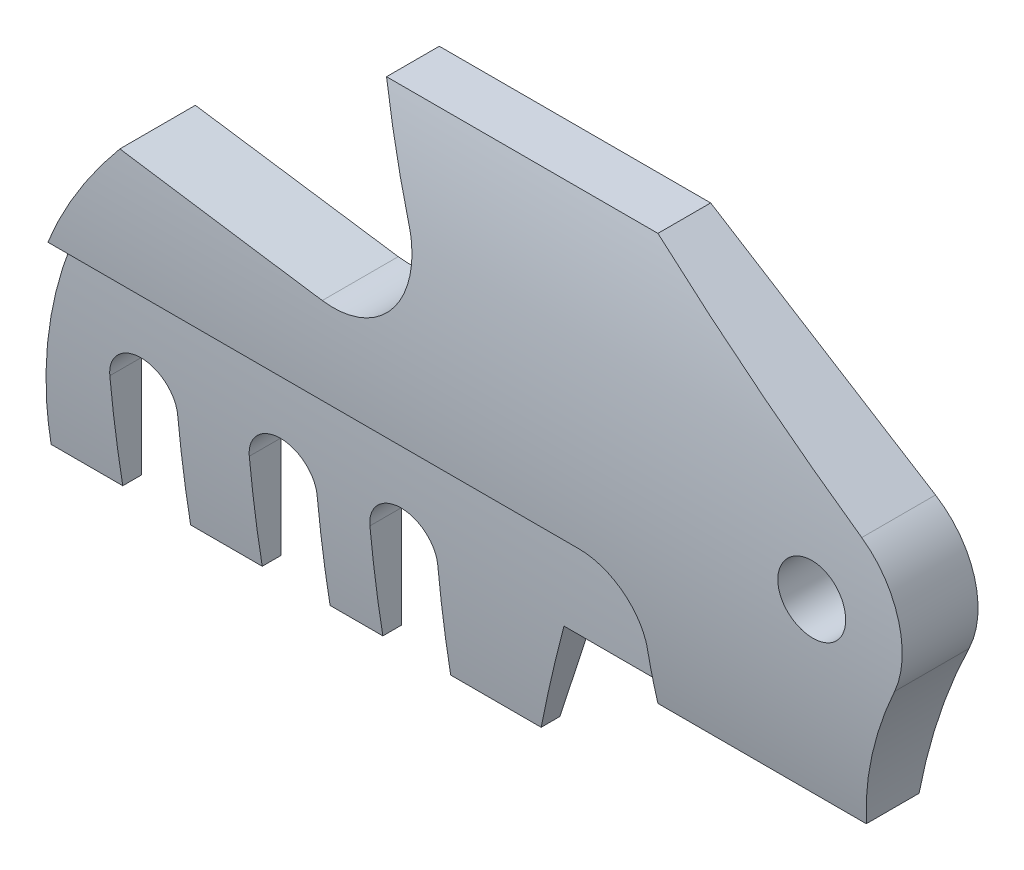
SolidWorks part; units mm, degrees
ref_plane "前视基准面" through (0, 0, 0) normal (0, 0, 1) x (1, 0, 0)
ref_plane "上视基准面" through (0, 0, 0) normal (0, 1, 0) x (1, 0, 0)
ref_plane "右视基准面" through (0, 0, 0) normal (1, 0, 0) x (0, 0, -1)
other "Configuration Table"
sketch "草图1" plane through (0, 0, 0) normal (0, 0, 1) x (1, 0, 0)
  line L0 (-42.3599, 46.0357) -> (-15.4451, 42.105)
  line L1 (-4.7081, 55.696) -> (-10, 69)
  line L2 (-10, 69) -> (26, 69)
  line L3 (26, 69) -> (55.8268, 50.3622)
  line L4 (-52.4523, 30) -> (18, 30)
  line L5 (26, 22) -> (26, 15)
  line L6 (26, 15) -> (53.646, 15)
  line L7 (26, 15) -> (10.8738, 15)
  line L8 (10.8738, 15) -> (6, 0)
  line L9 (6, 0) -> (-6, 0)
  line L10 (-6, 0) -> (-6, 13.5)
  line L11 (-15, 13.5) -> (-15, 0)
  line L12 (-15, 0) -> (-22, 0)
  line L13 (-22, 0) -> (-22, 13.5)
  line L14 (-31, 13.5) -> (-31, 0)
  line L15 (-31, 0) -> (-40.5, 0)
  line L16 (-49.5, 13.5) -> (-49.5, 0)
  line L17 (-40.5, 0) -> (-40.5, 13.5)
  line L18 (-49.5, 0) -> (-59, 0)
  arc A0 (-59, 0) -> (-42.3599, 46.0357) centre (13, 0) cw
  arc A1 (-15.4451, 42.105) -> (-4.7081, 55.696) centre (-14, 52) ccw
  arc A2 (18, 30) -> (26, 22) centre (18, 22) cw
  arc A3 (-6, 13.5) -> (-15, 13.5) centre (-10.5, 13.5) ccw
  arc A4 (-22, 13.5) -> (-31, 13.5) centre (-26.5, 13.5) ccw
  arc A5 (-40.5, 13.5) -> (-49.5, 13.5) centre (-45, 13.5) ccw
  circle A6 centre (49.4678, 40.1856) radius 4.5
  arc A7 (55.8268, 50.3622) -> (60.2625, 34.944) centre (49.4678, 40.1856) cw
  arc A8 (60.2625, 34.944) -> (53.646, 15) centre (132.2272, 0) ccw
  point P31 (61, 43.5033)
  point P34 (0, 0)
  point P35 (46.4623, 15)
  point P38 (45.8803, 15)
  point P39 (0, 0)
  point P40 (-55.267, 50.5126)
  point P41 (0, 0)
  point P44 (0, 0)
  point P45 (68.7942, 15)
  point P46 (0, 0)
  dimension "D1" = 72
  dimension "D2" = 10
  dimension "D8" = 8
  dimension "D12" = 9
  dimension "D13" = 13.5
  dimension "D21" = 9
  dimension "D22" = 12
  dimension "D24" = 80
  dimension "D3" = 60
  dimension "D4" = 30
  dimension "D5" = 85
  dimension "D6" = 36
  dimension "D7" = 32
  dimension "D9" = 15
  dimension "D10" = 12
  dimension "D11" = 65
  dimension "D14" = 16
  dimension "D16" = 49
  dimension "D17" = 45
  dimension "D18" = 72
  dimension "D19" = 52
  dimension "D20" = 69
  dimension "D23" = 120
  dimension "D15" = 2
extrude "凸台-拉伸1" add sketch "草图1" along normal blind 20 contours A8 A7 L3 L2 L1 A1 L0 A0 L4 A2 L5 L6 A6 region at (15.8837, 42.2126, 0)
sketch "草图2" plane through (0, 0, 0) normal (1, 0, 0) x (0, 0, -1)
  line L0 (-20, 69) -> (0, 69) construction
  line L1 (-20, 15) -> (0, 15) construction
  line L2 (-20, 69) -> (-20, 50.3622) construction
  circle A0 centre (109.9231, 42) radius 120
  point P2 (-7, 69)
  point P5 (-7, 15)
  point P12 (0, 0)
  dimension "D1" = 240
  dimension "D2" = 13
extrude "切除-拉伸1" cut sketch "草图2" against normal through all both and the other way through all flip side to cut
shell "抽壳1" thickness 2 removed face at (12.3432, 39.9252, 0)
extrude "凸台-拉伸2" add sketch "草图1<3>" along normal blind 10 separate body contours A5 L17 L15 L14 A4 L13 L12 L11 A3 L10 L9 L8 L7 L5 A2 L4 A0 L18 L16 region at (-17.5521, 17.4976, 0)
sketch "草图1<3>" plane through (0, 0, 0) normal (0, 0, 1) x (1, 0, 0) same geometry as "草图1"
sketch "草图3" plane through (0, 0, 0) normal (1, 0, 0) x (0, 0, -1)
  line L0 (-10, 0) -> (0, 0) construction
  line L1 (-7.6525, 32) -> (0, 32) construction
  line L2 (-7.6525, 32) -> (0, 32) construction
  line L6 (-5.0635, 32) -> (-5.0635, 38.2521) construction
  arc A1 (-5.0635, 32) -> (-2.4869, 0) centre (194.9365, 32) ccw
  arc A2 (-9.8693, 34.944) -> (-7, 15) centre (109.9231, 42) ccw construction
  point P2 (193.6061, 47.1663)
  point P4 (-1.0968, 0)
  point P9 (0, 0)
  point P14 (-2.8342, 32)
  dimension "D2" = 200
extrude "切除-拉伸3" cut sketch "草图3" against normal through all and the other way through all flip side to cut
